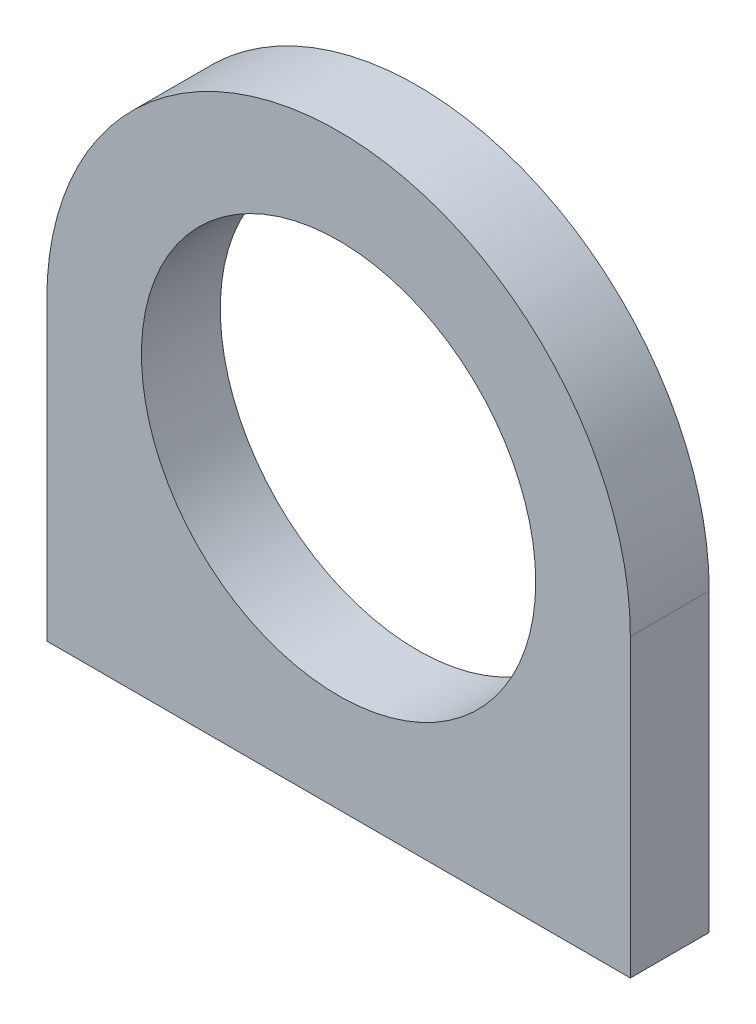
SolidWorks part; units mm, degrees
material "6061-T4 (SS)"
ref_plane "Front Plane" through (0, 0, 0) normal (0, 0, 1) x (1, 0, 0)
ref_plane "Top Plane" through (0, 0, 0) normal (0, 1, 0) x (1, 0, 0)
ref_plane "Right Plane" through (0, 0, 0) normal (1, 0, 0) x (0, 0, -1)
sketch "Sketch1" plane through (0, 0, 0) normal (0, 0, 1) x (1, 0, 0)
  line L0 (-18.5, 0) -> (-18.5, -18.75)
  line L1 (18.5, 0) -> (18.5, -18.75)
  line L2 (18.5, -18.75) -> (-18.5, -18.75)
  circle A0 centre (0, 0) radius 12.5
  circle A1 centre (0, 0) radius 18.5
  dimension "D1" = 25
  dimension "D2" = 37
  dimension "D3" = 18.75
extrude "Boss-Extrude1" add sketch "Sketch1" along normal blind 2.5 and the other way blind 2.5 contours A1 L0 L2 L1 | A1 A0 region at (0, -18.5415, 0) region at (0, 17.9767, 0)
sketch "Sketch2" plane through (0, -18.75, 0) normal (0, -1, 0) x (1, 0, 0)
  line L0 (0, -2.5) -> (0, 2.5)
  line L1 (18.5, -2.5) -> (-18.5, -2.5) construction
  line L2 (18.5, 2.5) -> (-18.5, 2.5) construction
  line L3 (0, 2.5) -> (0, 0)
  line L4 (0, 0) -> (-18.5, 0)
  line L5 (-18.5, 2.5) -> (-18.5, -2.5) construction
  circle A0 centre (-18.5, 0) radius 2.5
  circle A1 centre (-16, 0) radius 1.5
  point P11 (-16, 0)
  dimension "D1" = 5
  dimension "D2" = 3
extrude "Cut-Extrude1" cut sketch "Sketch2" against normal blind 10 contours A1
mirror "Mirror1" about plane through (0, 0, 0) normal (1, 0, 0) of "Cut-Extrude1"
